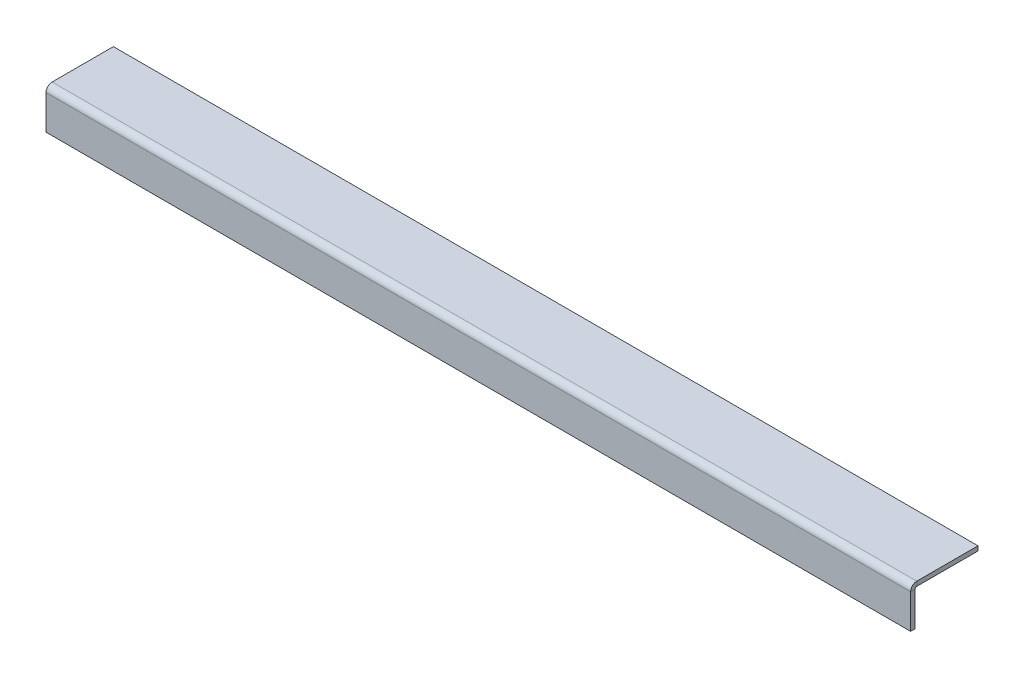
SolidWorks part; units mm, degrees
note: The reader was unsure of these and kept them because the rebuilt part matched: flange length of "Edge-Flange2".
ref_plane "Front Plane" through (0, 0, 0) normal (0, 0, 1) x (1, 0, 0)
ref_plane "Top Plane" through (0, 0, 0) normal (0, 1, 0) x (1, 0, 0)
ref_plane "Right Plane" through (0, 0, 0) normal (1, 0, 0) x (0, 0, -1)
sketch "Sketch1" plane through (0, 0, 0) normal (0, 1, 0) x (1, 0, 0)
  line L1 (-192.5, 30) -> (192.5, 30)
  line L2 (-192.5, 30) -> (-192.5, 0)
  line L3 (-192.5, 0) -> (192.5, 0)
  line L4 (192.5, 30) -> (192.5, 0)
  dimension "D1" = 385
  dimension "D2" = 192.5
  dimension "D3" = 30
base flange "Base-Flange1" sketch "Sketch1" thickness 2 reverse thickness direction no parameters "D1"=0.7366
edge flange "Edge-Flange2" sketch "Sketch11" flange angle 90 flange length 18 flange position material inside bend radius 0.7366 thickness 2 relief rectangular parameters "D6"=10
sketch "Sketch11" plane through (0, -2, 0) normal (0, 0, 1) x (-1, 0, 0)
  line L0 (192.5, 0) -> (-192.5, 0) construction
  line L1 (192.5, 0) -> (-192.5, 0)
  line L2 (-192.5, 0) -> (-192.5, 16)
  line L3 (-192.5, 16) -> (192.5, 16)
  line L4 (192.5, 16) -> (192.5, 0)
bend "EdgeBend2" bend radius 0.7366 bend angle 90 parameters "D5"=2
sketch "Bend-Lines1" [suppressed] plane through (0, 0, 0) normal (0, 1, 0) x (1, 0, 0)
sketch "Bounding-Box1" [suppressed] plane through (0, 0, 0) normal (0, 1, 0) x (1, 0, 0)
sheet metal parameters "Sheet-Metal1" thickness 2 parameters "D1"=0.7366
flat pattern "Flat-Pattern1" [suppressed]
sketch "Bend-Lines2" plane through (0, 0, 0) normal (0, 1, 0) x (1, 0, 0)
sketch3d "Bounding-Box2" [suppressed]
  line L0 (-192.5, 0, 0) -> (192.5, 0, 0) construction
  line L1 (-192.5, 100, 0) -> (192.5, 100, 0) construction
  line L2 (-192.5, 0, 0) -> (-192.5, 100, 0) construction
  line L3 (192.5, 0, 0) -> (192.5, 100, 0) construction
sheet metal parameters "Sheet-Metal3" thickness 2 parameters "D1"=0.7366
flat pattern "Flat-Pattern1"
sketch "Bend-Lines2" plane through (0, 0, 0) normal (0, 1, 0) x (1, 0, 0)
  line L2 (-192.5, 1.3727) -> (192.5, 1.3727) construction
  line L3 (-192.5, 1.3727) -> (192.5, 1.3727) construction
sketch3d "Bounding-Box2" [suppressed]
  line L0 (192.5, -15.2546, 0) -> (-192.5, -15.2546, 0) construction
  line L1 (192.5, 30, 0) -> (-192.5, 30, 0) construction
  line L2 (192.5, -15.2546, 0) -> (192.5, 30, 0) construction
  line L3 (-192.5, -15.2546, 0) -> (-192.5, 30, 0) construction
bend of the flat pattern "Flatten-<EdgeBend2>1"
